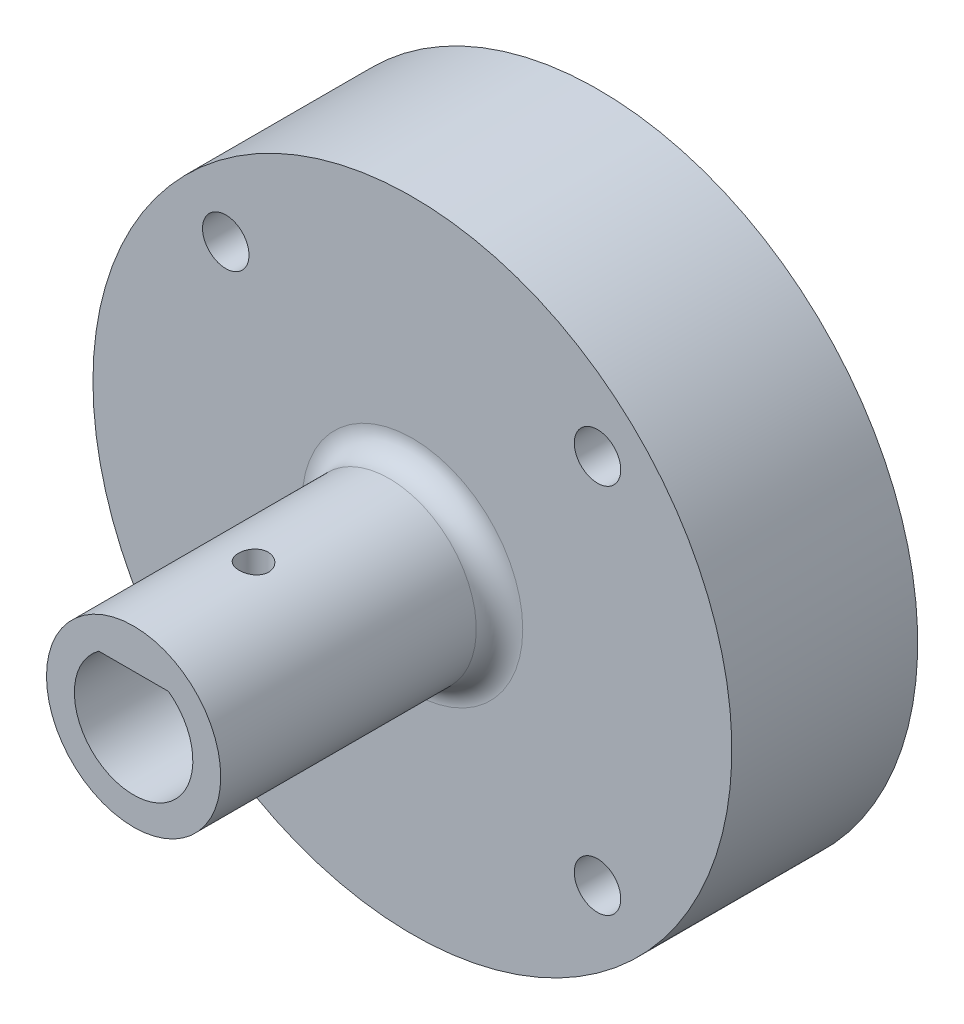
SolidWorks part; units mm, degrees
ref_plane "Front Plane" through (0, 0, 0) normal (0, 0, 1) x (1, 0, 0)
ref_plane "Top Plane" through (0, 0, 0) normal (0, 1, 0) x (1, 0, 0)
ref_plane "Right Plane" through (0, 0, 0) normal (1, 0, 0) x (0, 0, -1)
sketch "Sketch1" plane through (0, 0, 0) normal (0, 0, 1) x (1, 0, 0)
  circle A0 centre (0, 0) radius 7.5
  circle A1 centre (0, 0) radius 5.1
  dimension "D1" = 15
  dimension "D2" = 10.2
extrude "Boss-Extrude1" add sketch "Sketch1" along normal blind 24
sketch "Sketch2" plane through (0, 0, 24) normal (0, 0, 1) x (1, 0, 0)
  line L0 (-8.1162, 0) -> (10.0877, 0) construction
  line L1 (-3, 4.1243) -> (3, 4.1243)
  circle A0 centre (0, 0) radius 5.1 construction
  arc A1 (-3, 4.1243) -> (3, 4.1243) centre (0, 0) cw
  circle M4 centre (0, 0) radius 5.1
  dimension "D1" = 6
extrude "Boss-Extrude2" add sketch "Sketch2" against normal blind 20 contours L1 M4 region at (0, 4.518, 24)
sketch "Sketch3" plane through (0, 4.1243, 0) normal (0, -1, 0) x (1, 0, 0)
  line L0 (5.1, 24) -> (-5.1, 24) construction
  circle A0 centre (0.3222, 14) radius 1.3
  dimension "D1" = 2.6
  dimension "D2" = 10
extrude "Cut-Extrude1" cut sketch "Sketch3" against normal blind 24
sketch "Sketch4" plane through (0, 0, 0) normal (0, 0, -1) x (-1, 0, 0)
  circle A0 centre (0, 0) radius 27.5
  dimension "D1" = 55
extrude "Boss-Extrude3" add sketch "Sketch4" along normal blind 16
fillet "Fillet1" radius 2 1 edges at (7.5, 0, 0)
sketch "Sketch5" plane through (0, 0, -16) normal (0, 0, -1) x (-1, 0, 0)
  arc A0 (-17.9353, -15.8868) -> (-13.9353, -15.8868) centre (-15.9353, -15.8868) ccw
  arc A1 (-13.9353, -15.8868) -> (-17.9353, -15.8868) centre (-15.9353, -15.8868) ccw
  arc A2 (14.0647, -15.8868) -> (18.0647, -15.8868) centre (16.0647, -15.8868) ccw
  arc A3 (18.0647, -15.8868) -> (14.0647, -15.8868) centre (16.0647, -15.8868) ccw
  arc A4 (18.0647, 16.1132) -> (14.0647, 16.1132) centre (16.0647, 16.1132) ccw
  arc A5 (14.0647, 16.1132) -> (18.0647, 16.1132) centre (16.0647, 16.1132) ccw
  arc A6 (-13.9353, 16.1132) -> (-17.9353, 16.1132) centre (-15.9353, 16.1132) ccw
  arc A7 (-17.9353, 16.1132) -> (-13.9353, 16.1132) centre (-15.9353, 16.1132) ccw
extrude "Cut-Extrude2" cut sketch "Sketch5" against normal blind 20
